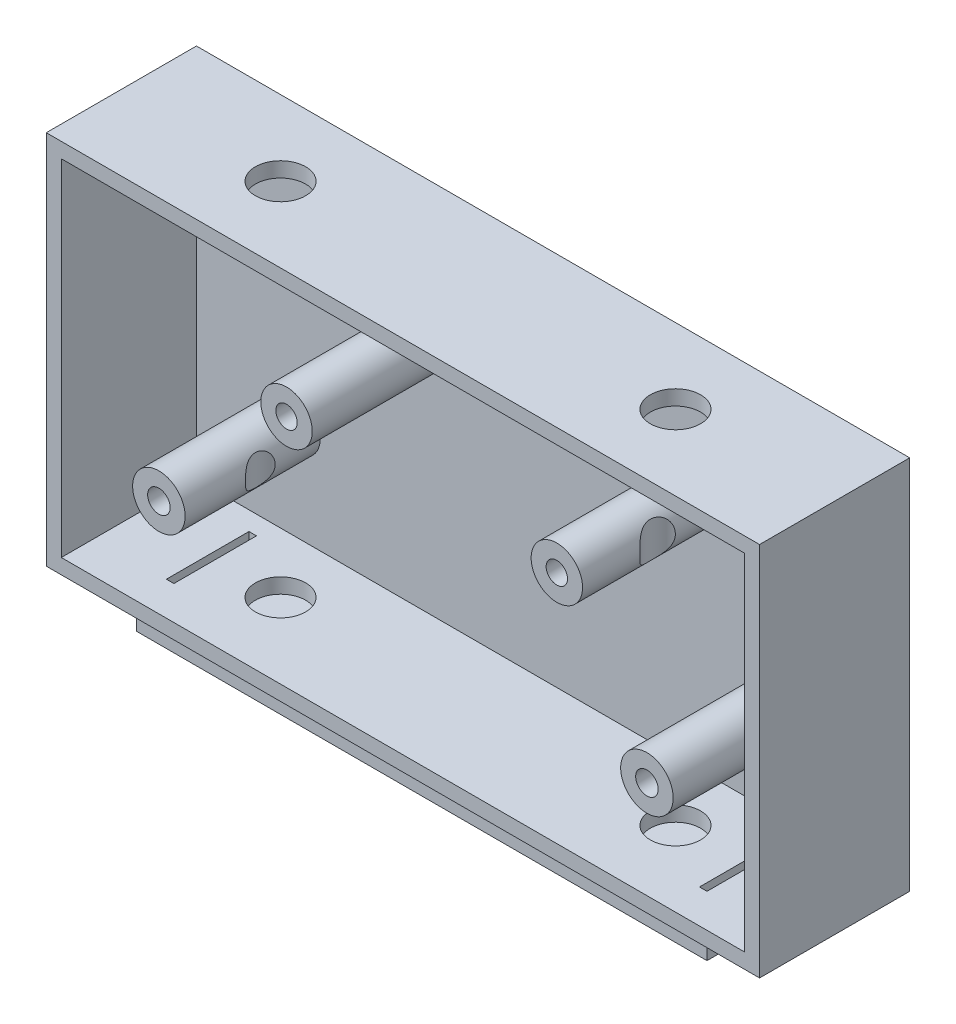
SolidWorks part; units mm, degrees
ref_plane "Front Plane" through (0, 0, 0) normal (0, 0, 1) x (1, 0, 0)
ref_plane "Top Plane" through (0, 0, 0) normal (0, 1, 0) x (1, 0, 0)
ref_plane "Right Plane" through (0, 0, 0) normal (1, 0, 0) x (0, 0, -1)
sketch "Sketch1" plane through (0, 0, 0) normal (0, 0, 1) x (1, 0, 0)
  line L1 (47.5, -25) -> (-47.5, -25)
  line L2 (47.5, -25) -> (47.5, 25)
  line L3 (47.5, 25) -> (-47.5, 25)
  line L4 (-47.5, -25) -> (-47.5, 25)
  line L5 (47.5, -25) -> (-47.5, 25) construction
  line L6 (47.5, 25) -> (-47.5, -25) construction
  point P0 (0, 0)
  dimension "D1" = 50
  dimension "D2" = 95
extrude "Boss-Extrude1" add sketch "Sketch1" along normal blind 20
sketch "Sketch4" plane through (0, 0, 0) normal (0, 0, -1) x (-1, 0, 0)
  circle A0 centre (15.5, 8.25) radius 1.425
  dimension "D1" = 2.85
extrude "Cut-Extrude3" cut sketch "Sketch4" against normal through all
pattern_linear "LPattern1" count 2 spacing 36 along (1, 0, 0) of "Cut-Extrude3"
sketch "Sketch5" plane through (0, 0, 0) normal (0, 0, -1) x (-1, 0, 0)
  line L0 (0, 0) -> (0, -27.1193) construction
  line L1 (47.5, 25) -> (47.5, -25) construction
  line L2 (47.5, -25) -> (-47.5, -25) construction
  circle A0 centre (-32.5, -10) radius 1.5
  circle A1 centre (32.5, -10) radius 1.5
  dimension "D2" = 3
  dimension "D1" = 65
  dimension "D3" = 15
extrude "Cut-Extrude4" cut sketch "Sketch5" against normal through all
sketch "Sketch6" plane through (0, -25, 0) normal (0, -1, 0) x (1, 0, 0)
  line L0 (-47.5, 20) -> (47.5, 20) construction
  line L1 (38, 2.5) -> (33, 2.5)
  line L2 (38, 2.5) -> (38, 17.5)
  line L3 (38, 17.5) -> (33, 17.5)
  line L4 (33, 2.5) -> (33, 17.5)
  line L5 (38, 2.5) -> (33, 17.5) construction
  line L6 (38, 17.5) -> (33, 2.5) construction
  line L8 (47.5, 20) -> (47.5, 0) construction
  point P0 (35.5, 10)
  dimension "D1" = 15
  dimension "D2" = 10
  dimension "D3" = 5
  dimension "D4" = 12
extrude "Boss-Extrude2" add sketch "Sketch6" along normal blind 2
mirror "Mirror1" about plane through (0, 0, 0) normal (1, 0, 0) of "Boss-Extrude2"
sketch "Sketch7" plane through (0, -27, 0) normal (0, -1, 0) x (1, 0, 0)
  line L1 (-38, 17.5) -> (38, 17.5)
  line L2 (-38, 17.5) -> (-38, 2.5)
  line L3 (-38, 2.5) -> (38, 2.5)
  line L4 (38, 17.5) -> (38, 2.5)
extrude "Boss-Extrude3" add sketch "Sketch7" along normal blind 2
shell "Shell1" thickness 2 removed face at (31, -10, 20)
sketch "Sketch2" plane through (0, -25, 0) normal (0, -1, 0) x (1, 0, 0)
  line L0 (-47.5, 0) -> (47.5, 0) construction
  line L1 (-47.5, 20) -> (-47.5, 0) construction
  line L2 (0, 0) -> (0, 35.0524) construction
  circle A0 centre (-26.3, 10) radius 3.35
  circle A1 centre (26.3, 10) radius 3.35
  dimension "D2" = 6.7
  dimension "D1" = 10
  dimension "D3" = 21.2
extrude "Cut-Extrude1" cut sketch "Sketch2" against normal through all
sketch "Sketch10" plane through (0, -29, 0) normal (0, -1, 0) x (1, 0, 0)
  circle A0 centre (26.3, 10) radius 1.425
  circle A1 centre (-26.3, 10) radius 1.425
  dimension "D1" = 2.85
extrude "Cut-Extrude5" cut sketch "Sketch10" against normal through all both and the other way through all
